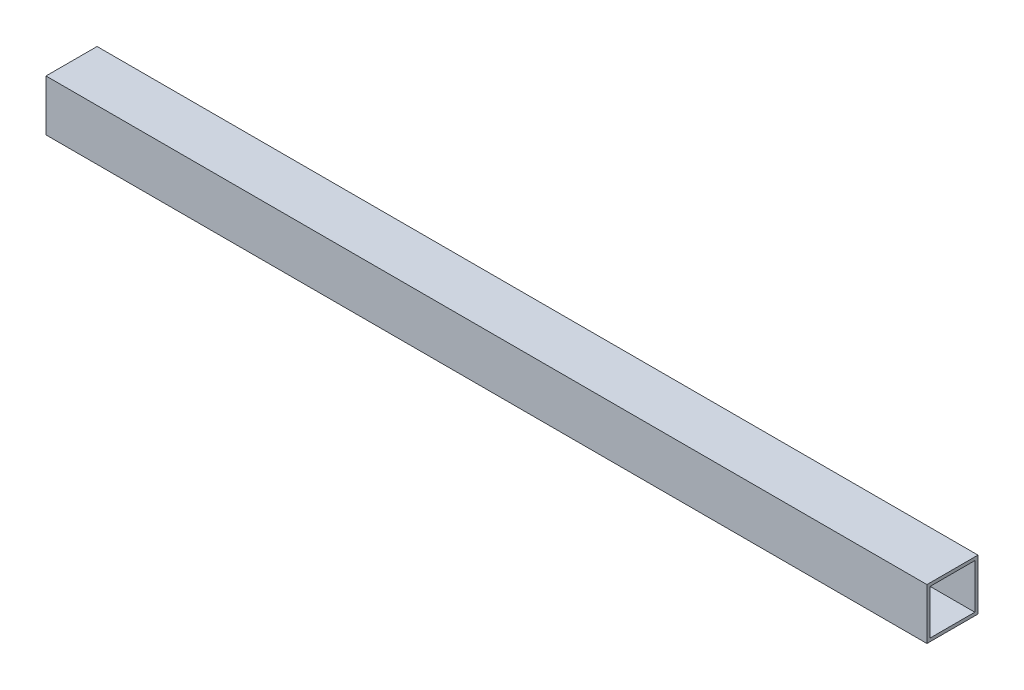
SolidWorks part; units mm, degrees
material "6063-T6"
ref_plane "Front Plane" through (0, 0, 0) normal (0, 0, 1) x (1, 0, 0)
ref_plane "Top Plane" through (0, 0, 0) normal (0, 1, 0) x (1, 0, 0)
ref_plane "Right Plane" through (0, 0, 0) normal (1, 0, 0) x (0, 0, -1)
sketch "Sketch1" plane through (0, 0, 0) normal (1, 0, 0) x (0, 0, -1)
  line L0 (3.175, 47.625) -> (47.625, 47.625)
  line L1 (0, 0) -> (50.8, 0)
  line L2 (0, 0) -> (0, 50.8)
  line L3 (0, 50.8) -> (50.8, 50.8)
  line L4 (50.8, 0) -> (50.8, 50.8)
  line L5 (47.625, 3.175) -> (47.625, 47.625)
  line L6 (3.175, 3.175) -> (47.625, 3.175)
  line L7 (3.175, 3.175) -> (3.175, 47.625)
  dimension "D1" = 50.8
  dimension "D2" = 50.8
  dimension "D3" = 3.175
extrude "Boss-Extrude1" add sketch "Sketch1" along normal blind 438.15 and the other way blind 438.15
